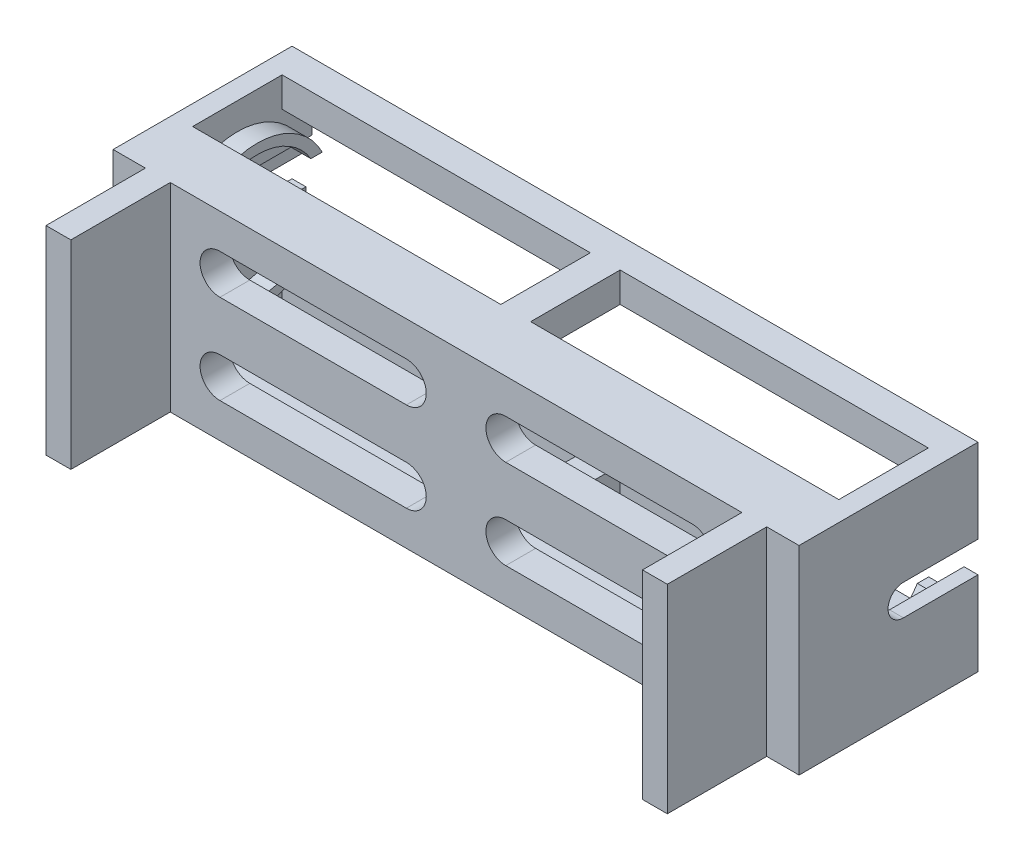
SolidWorks part; units mm, degrees
ref_plane "Plano frontal" through (0, 0, 0) normal (0, 0, 1) x (1, 0, 0)
ref_plane "Plano superior" through (0, 0, 0) normal (0, 1, 0) x (1, 0, 0)
ref_plane "Plano direito" through (0, 0, 0) normal (1, 0, 0) x (0, 0, -1)
sketch "Esboço1" plane through (0, 0, 0) normal (0, 0, 1) x (1, 0, 0)
  line L1 (32.5, -20) -> (-32.5, -20)
  line L2 (32.5, -20) -> (32.5, 20)
  line L3 (32.5, 20) -> (-32.5, 20)
  line L4 (-32.5, -20) -> (-32.5, 20)
  line L5 (32.5, -20) -> (-32.5, 20) construction
  line L6 (32.5, 20) -> (-32.5, -20) construction
  point P0 (0, 0)
  dimension "D1" = 65
  dimension "D2" = 40
extrude "Ressalto-extrusão1" add sketch "Esboço1" along normal blind 6
sketch "Esboço2" plane through (-32.5, 0, 0) normal (-1, 0, 0) x (0, 0, 1)
  line L0 (0, 20) -> (-30, 20)
  line L1 (-30, 20) -> (-30, -20)
  line L2 (-30, -20) -> (0, -20)
  line L4 (0, 20) -> (0, -20)
  line L5 (0, -20) -> (6, -20)
  line L6 (6, -20) -> (6, 20)
  line L7 (6, 20) -> (0, 20)
  line L8 (0, 20) -> (0, -20) construction
  line L9 (0, -20) -> (6, -20)
  line L10 (6, -20) -> (6, 20)
  line L11 (6, 20) -> (0, 20)
  dimension "D2" = 30
  dimension "D1" = 0
extrude "Ressalto-extrusão2" add sketch "Esboço2" along normal blind 4
sketch "Esboço3" plane through (-36.5, 0, 0) normal (-1, 0, 0) x (0, 0, 1)
  line L0 (0, 20) -> (0, -20) construction
  line L1 (0, 20) -> (0, -20) construction
  line L2 (-15, 3.1) -> (-30, 3.1)
  line L3 (0, 20) -> (-30, 20) construction
  line L4 (0, 20) -> (0, -20) construction
  line L5 (0, -20) -> (-30, -20) construction
  line L6 (-30, 20) -> (-30, -20) construction
  line L7 (-15, -20) -> (-15, 20) construction
  line L8 (0, 0) -> (-30, 0) construction
  line L9 (-30, 3.1) -> (-30, -3.1)
  line L10 (-30, -3.1) -> (-15, -3.1)
  arc A0 (-15, -3.1) -> (-15, 3.1) centre (-15, 0) ccw
  point P276 (-15, 0)
  dimension "D1" = 6.2
extrude "Corte-extrusão1" cut sketch "Esboço3" against normal through all
sketch "Esboço5" plane through (0, 0, 6) normal (0, 0, 1) x (1, 0, 0)
  line L0 (-36.5, -20) -> (32.5, -20) construction
  line L1 (-36.5, 20) -> (-30, 20)
  line L2 (-36.5, 20) -> (-36.5, -20)
  line L3 (-36.5, -20) -> (-30, -20)
  line L4 (-30, 20) -> (-30, -20)
  line L6 (-30, 20) -> (-25, 20)
  line L7 (-30, 20) -> (-30, -20)
  line L8 (-30, -20) -> (-25, -20)
  line L9 (-25, 20) -> (-25, -20)
  line L10 (-25, 20) -> (-21.5, 20)
  line L11 (-25, 20) -> (-25, -20)
  line L12 (-25, -20) -> (-21.5, -20)
  line L13 (-21.5, 20) -> (-21.5, -20)
  line M5 (32.5, 20) -> (-36.5, 20)
  line M7 (-36.5, -20) -> (32.5, -20)
  dimension "D1" = 15
  dimension "D2" = 6.5
  dimension "D3" = 5
extrude "Ressalto-extrusão4" add sketch "Esboço5" along normal blind 20 contours L9 L4 M5 M7 region at (-27.5, 0, 6)
sketch "Esboço7" plane through (-32.5, 0, 0) normal (1, 0, 0) x (0, 0, -1)
  line L0 (15, -6.5) -> (30, -6.5)
  line L1 (30, -3.1) -> (30, -20) construction
  line L2 (30, -6.5) -> (30, 6.5)
  line L3 (30, 20) -> (30, 3.1) construction
  line L4 (30, 6.5) -> (15, 6.5)
  arc A0 (15, 6.5) -> (15, -6.5) centre (15, 0) ccw
  dimension "D1" = 13
extrude "Corte-extrusão3" cut sketch "Esboço7" against normal blind 1.2
sketch "Esboço8" plane through (-32.5, 0, 0) normal (1, 0, 0) x (0, 0, -1)
  line L4 (15, -6.5) -> (30, -6.5) construction
  line L5 (25.794, -6.5) -> (28.0733, -6.5)
  line L6 (30, 6.5) -> (15, 6.5) construction
  line L7 (28.0733, 6.5) -> (25.794, 6.5)
  arc A0 (25.794, 6.5) -> (25.794, -6.5) centre (15, 0) ccw
  arc A1 (28.0733, 6.5) -> (28.0733, -6.5) centre (15, 0) ccw
  dimension "D1" = 25.2
  dimension "D2" = 2
extrude "Ressalto-extrusão5" add sketch "Esboço8" along normal blind 4
sketch "Esboço11" plane through (0, 0, 6) normal (0, 0, 1) x (1, 0, 0)
  line L0 (-15, 9) -> (22.5, 9) construction
  line L1 (-15, 13) -> (22.5, 13)
  line L2 (-15, 5) -> (22.5, 5)
  line L3 (-15, -9) -> (22.5, -9) construction
  line L4 (-15, -5) -> (22.5, -5)
  line L5 (-15, -13) -> (22.5, -13)
  line L6 (32.5, -20) -> (32.5, 20) construction
  line L7 (-25, 20) -> (-25, -20) construction
  line L8 (32.5, 20) -> (-25, 20) construction
  line L9 (-25, -20) -> (32.5, -20) construction
  line L10 (3.75, 20) -> (3.75, -20) construction
  arc A0 (-15, 13) -> (-15, 5) centre (-15, 9) ccw
  arc A1 (22.5, 5) -> (22.5, 13) centre (22.5, 9) ccw
  arc A2 (-15, -5) -> (-15, -13) centre (-15, -9) ccw
  arc A3 (22.5, -13) -> (22.5, -5) centre (22.5, -9) ccw
  point P2 (3.75, 9)
  point P7 (3.75, -9)
  dimension "D1" = 10
  dimension "D2" = 10
  dimension "D3" = 7
  dimension "D4" = 7
  dimension "D5" = 10
extrude "Corte-extrusão4" cut sketch "Esboço11" against normal through all
sketch "Esboço12" plane through (-32.5, 0, 0) normal (1, 0, 0) x (0, 0, -1)
  line L14 (0, -20) -> (6, -20)
  line L15 (0, -20) -> (0, -14)
  line L16 (0, -14) -> (6, -14)
  line L17 (6, -20) -> (6, -14)
  line L18 (30, -20) -> (24, -20)
  line L19 (30, -20) -> (30, -14)
  line L20 (30, -14) -> (24, -14)
  line L21 (24, -20) -> (24, -14)
  dimension "D1" = 6
  dimension "D2" = 6
extrude "Ressalto-extrusão6" add sketch "Esboço12" along normal up to surface (65 mm away) up to face at (32.5, 0, 3)
sketch "Esboço13" plane through (0, 0, -24) normal (0, 0, 1) x (1, 0, 0)
  line L0 (32.5, -14) -> (-32.5, -14) construction
  line L1 (32.5, -20) -> (29.5, -20)
  line L2 (32.5, -20) -> (32.5, -14)
  line L3 (32.5, -14) -> (29.5, -14)
  line L4 (29.5, -20) -> (29.5, -14)
  dimension "D1" = 3
extrude "Ressalto-extrusão7" add sketch "Esboço13" along normal up to surface (18 mm away) up to face at (0, -17, -6)
ref_plane "Plano1" through (0, 0, 0) normal (0, 1, 0) x (1, 0, 0)
sketch "Esboço14" plane through (0, 0, -24) normal (0, 0, 1) x (1, 0, 0)
  line L0 (29.5, -14) -> (-32.5, -14) construction
  line L1 (-4.5, -14) -> (1.5, -14)
  line L2 (-4.5, -14) -> (-4.5, -20)
  line L3 (-4.5, -20) -> (1.5, -20)
  line L4 (1.5, -14) -> (1.5, -20)
  line L5 (29.5, -20) -> (-32.5, -20) construction
  line L6 (-4.5, -17) -> (-32.5, -17) construction
  line L7 (-32.5, -14) -> (-32.5, -20) construction
  line L8 (1.5, -17) -> (29.5, -17) construction
  line L9 (29.5, -14) -> (29.5, -20) construction
mirror "Espelhar2" about plane through (0, 0, 0) normal (0, 1, 0) of "Ressalto-extrusão6", "Ressalto-extrusão7"
mirror "Espelhar1" about plane through (32.5, -20, 6) normal (-1, 0, 0) of "Corte-extrusão4", "Corte-extrusão1", "Ressalto-extrusão4", "Ressalto-extrusão2", "Ressalto-extrusão1", "Corte-extrusão3", "Ressalto-extrusão5", "Ressalto-extrusão6", "Ressalto-extrusão7", "Espelhar2"
